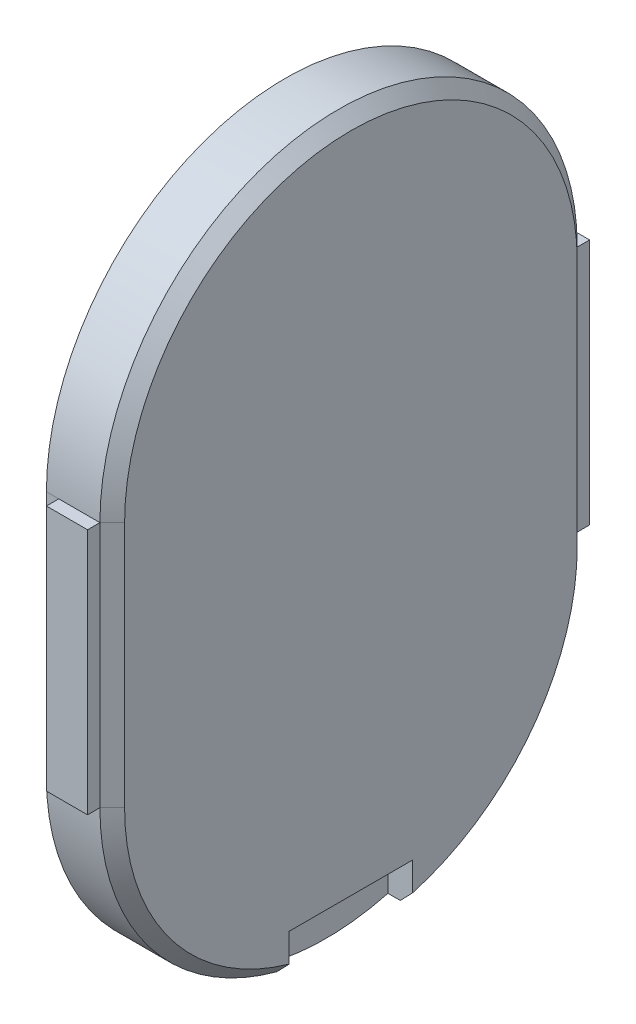
SolidWorks part; units mm, degrees
ref_plane "Front Plane" through (0, 0, 0) normal (0, 0, 1) x (1, 0, 0)
ref_plane "Top Plane" through (0, 0, 0) normal (0, 1, 0) x (1, 0, 0)
ref_plane "Right Plane" through (0, 0, 0) normal (1, 0, 0) x (0, 0, -1)
sketch "Sketch1" plane through (0, 0, 0) normal (1, 0, 0) x (0, 0, -1)
  line L0 (-73.2, 110) -> (-73.2, 116)
  line L1 (-61.6, 116) -> (-61.6, 110)
  arc A0 (-61.6, 110) -> (-67.4, 104.2) centre (-67.4, 110) cw
  arc A1 (-67.4, 104.2) -> (-73.2, 110) centre (-67.4, 110) cw
  arc A2 (-73.2, 116) -> (-67.4, 121.8) centre (-67.4, 116) cw
  arc A3 (-67.4, 121.8) -> (-61.6, 116) centre (-67.4, 116) cw
extrude "Boss-Extrude1" add sketch "Sketch1" along normal blind 1.6 from offset 61.4
chamfer "Chamfer1" distance 0.3 angle 45 4 edges at (63, 104.2, 67.4) (63, 113, 61.6) (63, 113, 73.2) (63, 121.8, 67.4)
sketch "Sketch2" plane through (0, 0, 0) normal (0, 0, 1) x (1, 0, 0)
  line L1 (61.7, 110) -> (62.7, 110)
  line L2 (61.7, 110) -> (61.7, 116)
  line L3 (61.7, 116) -> (62.7, 116)
  line L4 (62.7, 110) -> (62.7, 116)
extrude "Boss-Extrude2" add sketch "Sketch2" along normal blind 0.31 from offset 61.3
sketch "Sketch3" plane through (0, 0, 0) normal (0, 0, 1) x (1, 0, 0)
  line L1 (61.7, 110) -> (62.7, 110)
  line L2 (61.7, 110) -> (61.7, 116)
  line L3 (61.7, 116) -> (62.7, 116)
  line L4 (62.7, 110) -> (62.7, 116)
extrude "Boss-Extrude3" add sketch "Sketch3" along normal blind 0.31 from offset 73.19
sketch "Sketch4" plane through (0, 0, 0) normal (0, 0, 1) x (1, 0, 0)
  line L1 (62.4, 104.1) -> (63.1, 104.1)
  line L2 (62.4, 104.1) -> (62.4, 105.4)
  line L3 (62.4, 105.4) -> (63.1, 105.4)
  line L4 (63.1, 104.1) -> (63.1, 105.4)
extrude "Boss-Extrude4" add sketch "Sketch4" along normal blind 3 from offset 65.9 separate body
combine bodies "Combine1" operation type subtract main body 103 bodies to subtract 104
